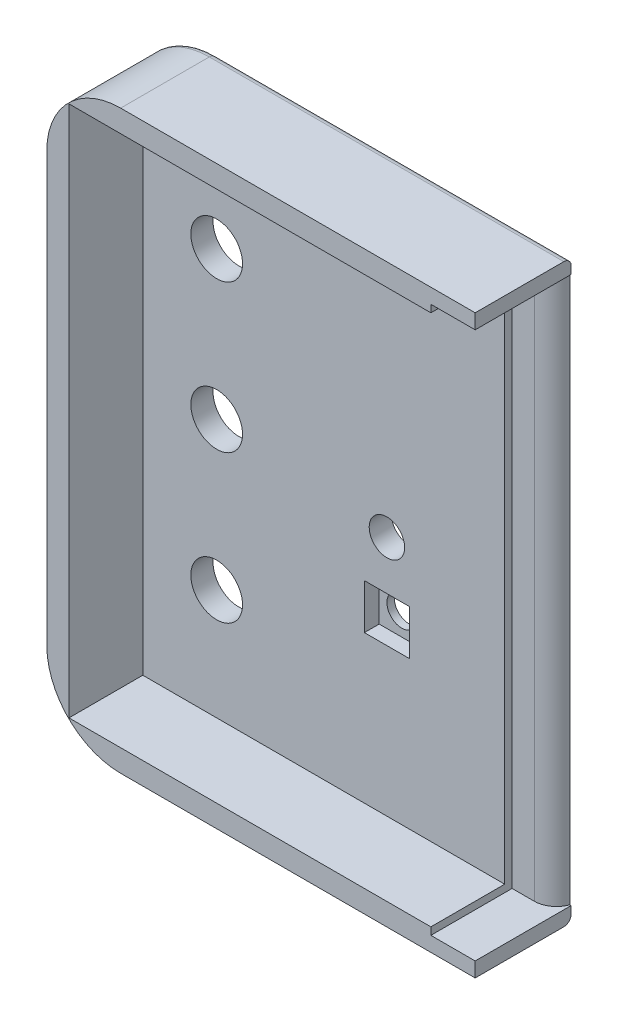
SolidWorks part; units mm, degrees
ref_plane "Front Plane" through (0, 0, 0) normal (0, 0, 1) x (1, 0, 0)
ref_plane "Top Plane" through (0, 0, 0) normal (0, 1, 0) x (1, 0, 0)
ref_plane "Right Plane" through (0, 0, 0) normal (1, 0, 0) x (0, 0, -1)
sketch "Sketch1" plane through (0, 0, 0) normal (0, 0, 1) x (1, 0, 0)
  line L1 (-69.875, 86.875) -> (-11.875, 86.875)
  line L2 (-69.875, 86.875) -> (-69.875, 8.875)
  line L3 (-69.875, 8.875) -> (-11.875, 8.875)
  line L4 (-11.875, 86.875) -> (-11.875, 8.875)
  dimension "D1" = 58
  dimension "D2" = 78
extrude "Boss-Extrude1" add sketch "Sketch1" along normal blind 13
sketch "Sketch2" plane through (0, 0, 13) normal (0, 0, 1) x (1, 0, 0)
  line L0 (-11.875, 8.875) -> (-11.875, 86.875) construction
  line L1 (-66.875, 83.875) -> (-14.875, 83.875)
  line L2 (-66.875, 83.875) -> (-66.875, 11.875)
  line L3 (-66.875, 11.875) -> (-14.875, 11.875)
  line L4 (-14.875, 83.875) -> (-14.875, 11.875)
  line L5 (-66.875, 83.875) -> (-14.875, 11.875) construction
  line L6 (-66.875, 11.875) -> (-14.875, 83.875) construction
  line L7 (-69.875, 8.875) -> (-11.875, 8.875) construction
  point P0 (-40.875, 47.875)
  dimension "D1" = 52
  dimension "D2" = 72
  dimension "D3" = 3
  dimension "D4" = 3
extrude "Cut-Extrude1" cut sketch "Sketch2" against normal blind 10
sketch "Sketch3" plane through (0, 0, 3) normal (0, 0, 1) x (1, 0, 0)
  line L0 (-66.875, 83.875) -> (-66.875, 11.875) construction
  line L1 (-66.875, 11.875) -> (-14.875, 11.875) construction
  circle A0 centre (-56.875, 66.875) radius 3.5
  circle A1 centre (-56.875, 46.875) radius 3.5
  circle A2 centre (-56.875, 26.875) radius 3.5
  dimension "D1" = 7
  dimension "D2" = 7
  dimension "D3" = 7
  dimension "D7" = 20
  dimension "D8" = 20
  dimension "D9" = 15
  dimension "D4" = 10
  dimension "D5" = 10
  dimension "D6" = 10
extrude "Cut-Extrude2" cut sketch "Sketch3" against normal blind 10
sketch "Sketch4" plane through (0, 0, 3) normal (0, 0, 1) x (1, 0, 0)
  line L0 (-66.875, 11.875) -> (-14.875, 11.875) construction
  line L1 (-36.875, 37.975) -> (-30.775, 37.975)
  line L2 (-36.875, 37.975) -> (-36.875, 31.875)
  line L3 (-36.875, 31.875) -> (-30.775, 31.875)
  line L4 (-30.775, 37.975) -> (-30.775, 31.875)
  circle A0 centre (-56.875, 26.875) radius 3.5 construction
  dimension "D1" = 6.1
  dimension "D2" = 6.1
  dimension "D3" = 20
  dimension "D4" = 20
extrude "Cut-Extrude3" cut sketch "Sketch4" against normal blind 2
sketch "Sketch5" plane through (0, 0, 1) normal (0, 0, 1) x (1, 0, 0)
  circle A1 centre (-33.825, 34.925) radius 2
  dimension "D1" = 4
extrude "Cut-Extrude4" cut sketch "Sketch5" against normal blind 2
sketch "Sketch6" plane through (0, 0, 0) normal (0, 0, -1) x (-1, 0, 0)
  circle A0 centre (33.825, 44.5692) radius 2.4
  dimension "D1" = 4.8
extrude "Cut-Extrude5" cut sketch "Sketch6" against normal blind 9
sketch "Sketch7" plane through (-11.875, 0, 0) normal (1, 0, 0) x (0, 0, -1)
  line L0 (0, 8.875) -> (0, 86.875) construction
  line L1 (-14.9081, 84.875) -> (-2, 84.875)
  line L2 (-14.9081, 84.875) -> (-14.9081, 10.875)
  line L3 (-14.9081, 10.875) -> (-2, 10.875)
  line L4 (-2, 84.875) -> (-2, 10.875)
  line L5 (-13, 86.875) -> (0, 86.875) construction
  line L6 (-13, 8.875) -> (0, 8.875) construction
  dimension "D1" = 2
  dimension "D2" = 2
  dimension "D3" = 2
extrude "Cut-Extrude6" cut sketch "Sketch7" against normal blind 6
fillet "Fillet1" radius 10 1 edges at (-69.875, 86.875, 6.5)
fillet "Fillet2" radius 10 1 edges at (-69.875, 8.875, 6.5)
fillet "Fillet3" radius 1 5 edges at (-35.875, 86.875, 0) (-66.9461, 83.9461, 0) (-69.875, 47.875, 0) (-66.9461, 11.8039, 0) (-35.875, 8.875, 0)
fillet "Fillet4" radius 3 1 edges at (-11.875, 47.875, 2)
sketch "Sketch8" plane through (0, 0, 0) normal (0, 0, -1) x (-1, 0, 0)
  circle A0 centre (56.875, 66.875) radius 3.5 construction
  text T0 "<b>B-left</b>"
  dimension "D1" = 20
extrude "Cut-Extrude7" cut sketch "Sketch8" against normal blind 1
sketch "Sketch9" plane through (0, 0, 0) normal (0, 0, -1) x (-1, 0, 0)
  circle A0 centre (56.875, 46.875) radius 3.5 construction
  text T0 "<b>Front</b>"
  dimension "D2" = 0
  dimension "D1" = 20
extrude "Cut-Extrude8" cut sketch "Sketch9" against normal blind 1
sketch "Sketch10" plane through (0, 0, 0) normal (0, 0, -1) x (-1, 0, 0)
  circle A1 centre (56.875, 26.875) radius 3.5 construction
  text T0 "<b>B-right</b>"
  point P5 (53.5763, 25.705)
  dimension "D1" = 20
extrude "Cut-Extrude9" cut sketch "Sketch10" against normal blind 1
sketch "Sketch11" plane through (0, 0, 0) normal (0, 0, -1) x (-1, 0, 0)
  circle A0 centre (33.825, 34.925) radius 2 construction
  text T0 "Manual"
  dimension "D1" = 0
  dimension "D2" = 21
extrude "Cut-Extrude10" cut sketch "Sketch11" against normal blind 1
